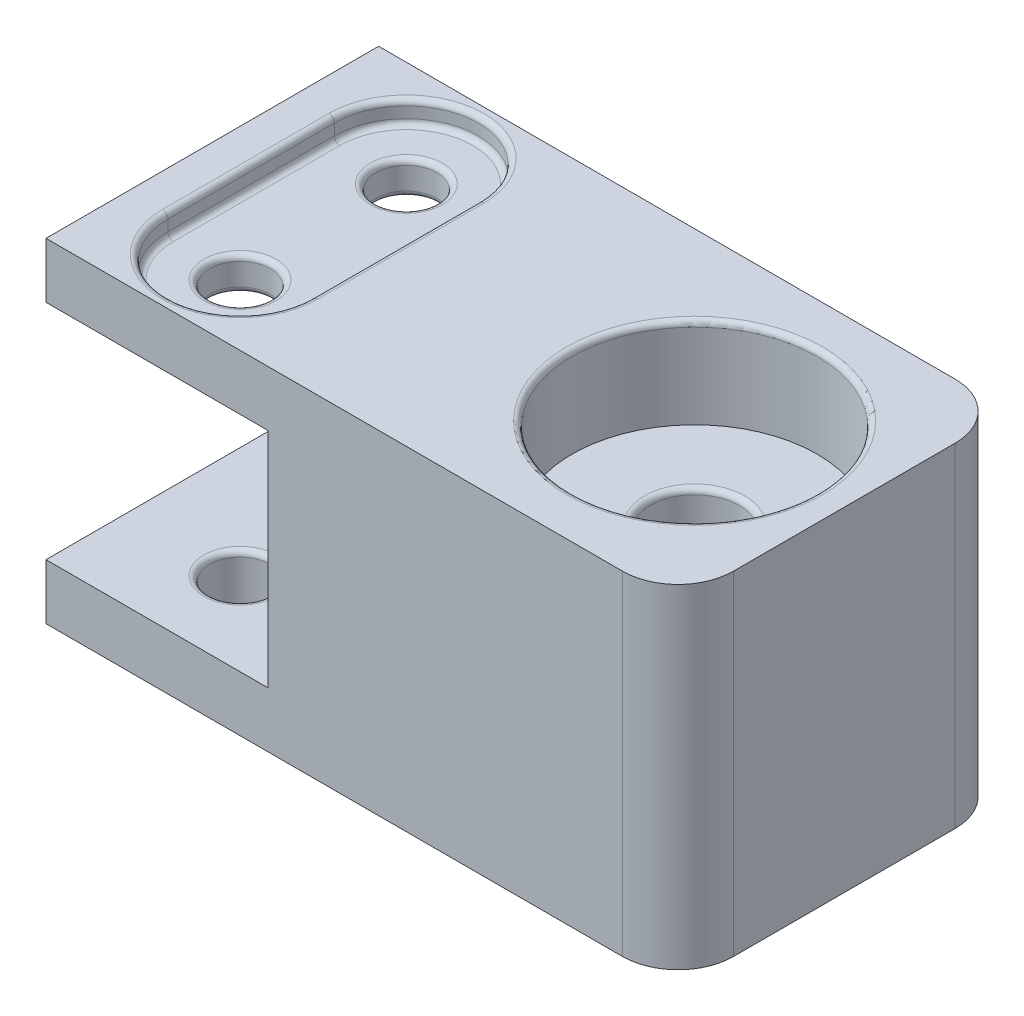
SolidWorks part; units mm, degrees
ref_plane "Front Plane" through (0, 0, 0) normal (0, 0, 1) x (1, 0, 0)
ref_plane "Top Plane" through (0, 0, 0) normal (0, 1, 0) x (1, 0, 0)
ref_plane "Right Plane" through (0, 0, 0) normal (1, 0, 0) x (0, 0, -1)
sketch "Sketch4" plane through (0, 0, 0) normal (0, 1, 0) x (1, 0, 0)
  line L1 (-28.5, -15) -> (28.5, -15)
  line L2 (-28.5, -15) -> (-28.5, 15)
  line L3 (-28.5, 15) -> (28.5, 15)
  line L4 (28.5, -15) -> (28.5, 15)
  line L5 (-28.5, -15) -> (28.5, 15) construction
  line L6 (-28.5, 15) -> (28.5, -15) construction
  point P0 (0, 0)
  dimension "D1" = 57
  dimension "D2" = 30
extrude "Boss-Extrude2" add sketch "Sketch4" along normal blind 5
sketch "Sketch5" plane through (0, 5, 0) normal (0, 1, 0) x (1, 0, 0)
  line L0 (-28.5, -15) -> (28.5, -15) construction
  line L1 (28.5, 15) -> (-8.5, 15)
  line L2 (28.5, 15) -> (28.5, -15)
  line L3 (28.5, -15) -> (-8.5, -15)
  line L4 (-8.5, 15) -> (-8.5, -15)
  line L5 (28.5, 15) -> (-8.5, -15) construction
  line L6 (28.5, -15) -> (-8.5, 15) construction
  line L7 (-28.5, 15) -> (-28.5, -15) construction
  point P4 (10, 0)
  dimension "D1" = 20
extrude "Boss-Extrude3" add sketch "Sketch5" along normal blind 20.1
sketch "Sketch6" plane through (0, 25.1, 0) normal (0, 1, 0) x (1, 0, 0)
  line L0 (28.5, -15) -> (28.5, 15) construction
  line L1 (28.5, 15) -> (-8.5, 15) construction
  line L3 (-8.5, -15) -> (28.5, -15) construction
  line L5 (-8.5, 15) -> (-28.5, 15) construction
  line L6 (-28.5, 15) -> (-28.5, -15) construction
  line L7 (-28.5, -15) -> (-8.5, -15) construction
  line L8 (28.5, -15) -> (28.5, 15)
  line L9 (28.5, 15) -> (-8.5, 15)
  line L11 (-8.5, -15) -> (28.5, -15)
  line L13 (-8.5, 15) -> (-28.5, 15)
  line L14 (-28.5, 15) -> (-28.5, -15)
  line L15 (-28.5, -15) -> (-8.5, -15)
extrude "Boss-Extrude4" add sketch "Sketch6" along normal blind 5
sketch "Sketch7" plane through (0, 30.1, 0) normal (0, 1, 0) x (1, 0, 0)
  line L0 (-28.5, -15) -> (28.5, -15) construction
  line L1 (-28.5, 15) -> (-28.5, -15) construction
  line L2 (-28.5, 0) -> (28.5, 0) construction
  line L3 (28.5, -15) -> (28.5, 15) construction
  circle A0 centre (-18.5, -7.5) radius 2.75
  circle A1 centre (-18.5, 7.5) radius 2.75
  dimension "D1" = 5.5
  dimension "D2" = 7.5
  dimension "D3" = 10
extrude "Cut-Extrude3" cut sketch "Sketch7" against normal through all
fillet "Fillet5" radius 0.5 8 edges at (-18.5, 5, -10.25) (-18.5, 0, -10.25) (-18.5, 5, 4.75) (-18.5, 0, 10.25) (-18.5, 25.1, -4.75) (-18.5, 30.1, -10.25) (-18.5, 25.1, 10.25) (-18.5, 30.1, 10.25)
sketch "Sketch8" plane through (0, 30.1, 0) normal (0, 1, 0) x (1, 0, 0)
  line L0 (-8.5, 15) -> (-8.5, -15) construction
  line L1 (-8.5, 15) -> (-8.5, -15) construction
  line L2 (28.5, -15) -> (28.5, 15) construction
  circle A1 centre (15, 0) radius 11.049
  dimension "D1" = 22.098
  dimension "D2" = 13.5
extrude "Cut-Extrude4" cut sketch "Sketch8" against normal blind 8.128 contours A1
fillet "Fillet6" radius 5 2 edges at (28.5, 15.05, -15) (28.5, 15.05, 15)
sketch "Sketch11" plane through (0, 0, 0) normal (0, -1, 0) x (1, 0, 0)
  circle A1 centre (15, 0) radius 11.049 construction
  circle A2 centre (15, 0) radius 11.049
extrude "Cut-Extrude5" cut sketch "Sketch11" against normal blind 8.128
sketch "Sketch12" plane through (0, 8.128, 0) normal (0, -1, 0) x (1, 0, 0)
  circle A0 centre (15, 0) radius 4.025
  circle A1 centre (15, 0) radius 11.049
  circle A4 centre (15, 0) radius 11.049
  dimension "D2" = 8.05
  dimension "D1" = 0
extrude "Cut-Extrude6" cut sketch "Sketch12" against normal through all contours A0 region at (15, 8.128, 0)
fillet "Fillet7" radius 0.5 4 edges at (15, 30.1, 11.049) (15, 8.128, -4.025) (15, 21.972, 4.025) (15, 0, -11.049)
sketch "Sketch13" plane through (0, 30.1, 0) normal (0, 1, 0) x (1, 0, 0)
  line L0 (-25, -7.5) -> (-25, 7.5)
  line L1 (-12, -7.5) -> (-12, 7.5)
  arc A0 (-25, -7.5) -> (-12, -7.5) centre (-18.5, -7.5) ccw
  arc A1 (-12, 7.5) -> (-25, 7.5) centre (-18.5, 7.5) ccw
  dimension "D1" = 13
extrude "Cut-Extrude7" cut sketch "Sketch13" against normal blind 2
fillet "Fillet8" radius 0.5 10 edges at (-12, 28.1, 0) (-18.5, 28.1, 14) (-25, 28.1, 0) (-12, 30.1, 0) (-18.5, 30.1, 14) (-25, 30.1, 0) (-18.5, 28.1, -14) (-18.5, 30.1, -14) (-18.5, 28.1, 10.25) (-18.5, 28.1, -4.75)
